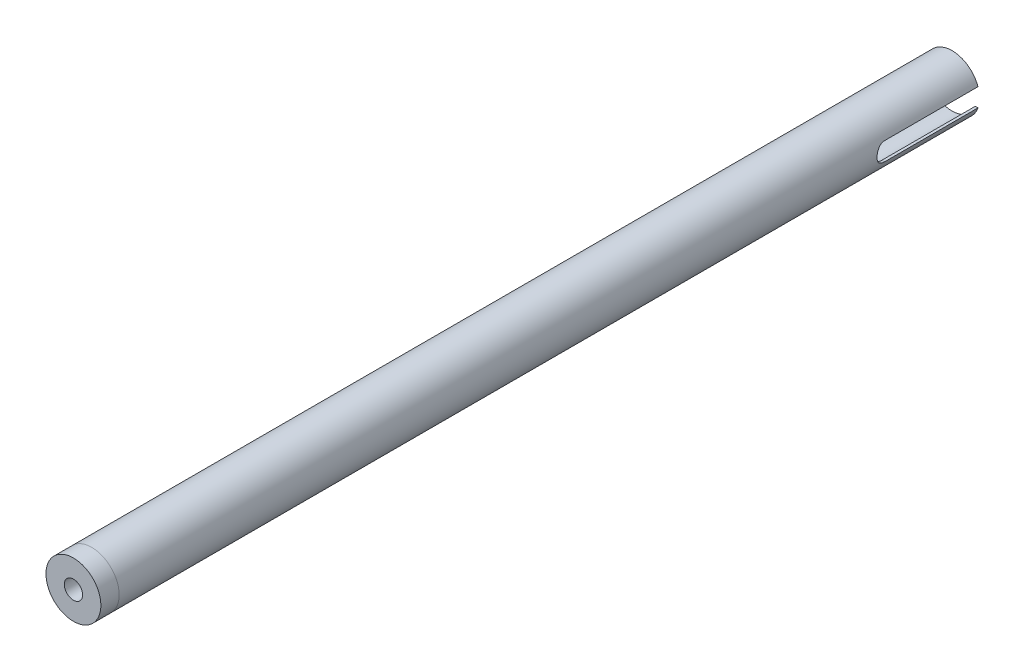
SolidWorks part; units mm, degrees
material "AISI 4130 Steel, normalized at 870C"
ref_plane "Front Plane" through (0, 0, 0) normal (0, 0, 1) x (1, 0, 0)
ref_plane "Top Plane" through (0, 0, 0) normal (0, 1, 0) x (1, 0, 0)
ref_plane "Right Plane" through (0, 0, 0) normal (1, 0, 0) x (0, 0, -1)
sketch "Axis" plane through (0, 0, 0) normal (0, 1, 0) x (1, 0, 0)
  line L0 (0, 0) -> (0, 304.6976) construction
  line L1 (0, 0) -> (0, -21.59) construction
  line L2 (0, 304.6976) -> (-9.525, 304.6976) construction
  line L3 (0, 332.6376) -> (-22.1542, 267.6518) construction
  dimension "D1" = 21.59
  dimension "D2" = 9.525
sketch "Sketch1" plane through (0, 0, 0) normal (0, 0, 1) x (1, 0, 0)
  line L0 (-9.525, 0) -> (9.525, 0) construction
  line L1 (-8.9803, 3.175) -> (8.9803, 3.175)
  line L2 (-8.9803, -3.175) -> (8.9803, -3.175)
  circle A0 centre (0, 0) radius 9.525
  circle A1 centre (0, 0) radius 8.636
  circle A2 centre (0, 0) radius 3.175
  dimension "D1" = 19.05
  dimension "D3" = 6.35
  dimension "D2" = 0.889
  dimension "D4" = 6.35
extrude "Threaded insert 1-1" add sketch "Sketch1" against normal blind 6.35 contours A2 L1 A1 | A1 L1 A0 | A2 L0 A1 L1 | A1 L0 A0 L1 | L0 A1 L2 A0 | L0 A2 L2 A1 | A2 L2 A1 | A1 L2 A0 | L0 A1 L2 A2 | L0 A0 L2 A1 | A0 L0 A1 L1 | A1 L0 A2 L1 region at (5.4259, 1.6615, 0) region at (5.4259, -1.6615, 0) region at (8.8881, 1.6046, 0) region at (8.8881, -1.6046, 0) region at (-5.4259, -1.6615, 0) region at (-5.4259, 1.6615, 0) region at (0, 5.4321, 0) region at (0, -5.4321, 0) region at (0, 8.8265, 0) region at (8.5057, -3.3655, 0) region at (-8.8881, -1.6046, 0) region at (-8.8881, 1.6046, 0)
extrude "Threaded insert 1-2" add sketch "Sketch1<3>" against normal blind 6.35 from surface contours A2 L1 A1 | A2 L0 A1 L1 | L0 A2 L2 A1 | A2 L2 A1 | L0 A1 L2 A2 | A1 L0 A2 L1 region at (5.4259, 1.6615, 0) region at (5.4259, -1.6615, 0) region at (-5.4259, -1.6615, 0) region at (-5.4259, 1.6615, 0) region at (0, 5.4321, 0) region at (0, -5.4321, 0) starting at face at (9.525, 0, -6.35)
sketch "Sketch1<3>" plane through (0, 0, 0) normal (0, 0, 1) x (1, 0, 0) same geometry as "Sketch1"
extrude "A-arm tube" add sketch "Sketch1<4>" against normal up to vertex (304.6976 mm away) from surface separate body contours A1 L1 A0 | A1 L0 A0 L1 | L0 A1 L2 A0 | A1 L2 A0 | L0 A0 L2 A1 | A0 L0 A1 L1 region at (8.8881, 1.6046, 0) region at (8.8881, -1.6046, 0) region at (0, 8.8265, 0) region at (8.5057, -3.3655, 0) region at (-8.8881, -1.6046, 0) region at (-8.8881, 1.6046, 0) up to point (0, 0, -304.6976) starting at face at (8.636, 0, -6.35)
sketch "Sketch1<4>" plane through (0, 0, 0) normal (0, 0, 1) x (1, 0, 0) same geometry as "Sketch1"
extrude "Apex slot" cut sketch "Sketch1<5>" along normal blind 35.56 from surface contours A0 L0 A1 L1 | L0 A0 L2 A1 | A1 L0 A0 L1 | L0 A1 L2 A0 region at (8.8881, 1.6046, 0) region at (8.8881, -1.6046, 0) region at (-8.8881, -1.6046, 0) region at (-8.8881, 1.6046, 0) starting at face at (8.636, 0, -304.6976)
sketch "Sketch1<5>" plane through (0, 0, 0) normal (0, 0, 1) x (1, 0, 0) same geometry as "Sketch1"
fillet "Fillet1" radius 3.175 4 edges at (-8.5057, 3.175, -269.1376) (-8.5057, -3.175, -269.1376) (8.5057, -3.175, -269.1376) (8.5057, 3.175, -269.1376)
equation "\"tube diameter\"= 3 / 4"
equation "\"tube thickness\"= .035"
equation "\"apex thickness\"= .25"
equation "\"tube slot\"= 1.4"
equation "\"D1@Sketch1\"=\"tube diameter\""
equation "\"D2@Sketch1\"=\"tube thickness\""
equation "\"threaded insert hole\" = 1 / 4"
equation "\"D3@Sketch1\"=\"threaded insert hole\""
equation "\"D4@Sketch1\"=\"apex thickness\""
equation "\"D1@Apex slot\" = \"tube slot\""
equation "\"D1@Fillet1\"=\"apex thickness\"/2"
equation "\"D2@Axis\"=\"tube diameter\"/2"
